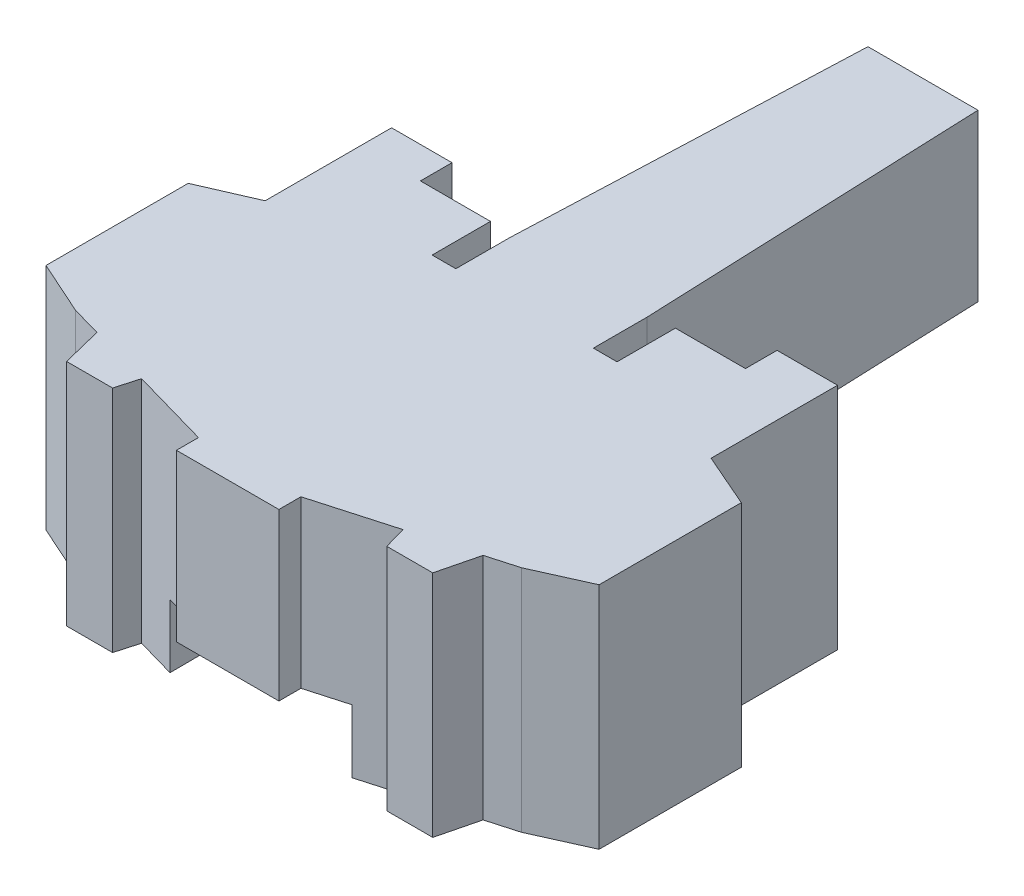
SolidWorks part; units mm, degrees
ref_plane "Front Plane" through (0, 0, 0) normal (0, 0, 1) x (1, 0, 0)
ref_plane "Top Plane" through (0, 0, 0) normal (0, 1, 0) x (1, 0, 0)
ref_plane "Right Plane" through (0, 0, 0) normal (1, 0, 0) x (0, 0, -1)
sketch "Sketch1" plane through (0, 0, 0) normal (0, 1, 0) x (1, 0, 0)
  line L0 (189.3756, 496.5449) -> (821.9605, 485.5031) construction
  line L1 (66.1046, 65.3579) -> (66.1046, 21.3579) construction
  line L2 (69.5865, 65.3579) -> (62.6228, 65.3579)
  line L3 (69.5865, 65.3579) -> (70.4558, 43.5381)
  line L4 (70.4558, 43.5381) -> (70.4558, 40.1478)
  line L5 (70.4558, 40.1478) -> (71.9558, 40.1478)
  line L6 (71.9558, 40.1478) -> (71.9558, 43.8392)
  line L7 (71.9558, 43.8392) -> (76.3893, 43.8392)
  line L8 (76.3893, 43.8392) -> (76.3893, 45.8392)
  line L9 (76.3893, 45.8392) -> (80.2143, 45.8392)
  line L10 (80.2143, 45.8392) -> (80.2143, 37.8392)
  line L11 (80.2143, 37.8392) -> (83.6046, 36.3613)
  line L12 (83.6046, 36.3613) -> (83.6046, 27.3613)
  line L13 (83.6046, 27.3613) -> (80.2143, 25.8392)
  line L14 (80.2143, 25.8392) -> (78.3232, 25.3017)
  line L15 (69.3478, 22.751) -> (69.3478, 21.3579)
  line L16 (69.3478, 21.3579) -> (62.8614, 21.3579)
  line L17 (62.8614, 22.751) -> (62.8614, 21.3579)
  line L18 (51.9949, 25.8392) -> (53.8861, 25.3017)
  line L19 (48.6046, 27.3613) -> (51.9949, 25.8392)
  line L20 (48.6046, 36.3613) -> (48.6046, 27.3613)
  line L21 (51.9949, 37.8392) -> (48.6046, 36.3613)
  line L22 (51.9949, 45.8392) -> (51.9949, 37.8392)
  line L23 (55.8199, 45.8392) -> (51.9949, 45.8392)
  line L24 (55.8199, 43.8392) -> (55.8199, 45.8392)
  line L25 (60.2534, 43.8392) -> (55.8199, 43.8392)
  line L26 (60.2534, 40.1478) -> (60.2534, 43.8392)
  line L27 (61.7534, 40.1478) -> (60.2534, 40.1478)
  line L28 (61.7534, 43.5381) -> (61.7534, 40.1478)
  line L29 (62.6228, 65.3579) -> (61.7534, 43.5381)
  line L30 (78.3232, 25.3017) -> (77.6888, 22.751)
  line L31 (77.6888, 22.751) -> (74.7811, 22.751)
  line L32 (74.7811, 22.751) -> (74.375, 24.1797)
  line L33 (74.375, 24.1797) -> (69.3478, 22.751)
  line L34 (53.8861, 25.3017) -> (54.5204, 22.751)
  line L35 (54.5204, 22.751) -> (57.4282, 22.751)
  line L36 (57.4282, 22.751) -> (57.8342, 24.1797)
  line L37 (57.8342, 24.1797) -> (62.8614, 22.751)
  dimension "D1" = 17.5
  dimension "D2" = 12
  dimension "D3" = 3.0881
  dimension "D4" = 1.4778
  dimension "D5" = 8
  dimension "D6" = 2
  dimension "D7" = 1.5
  dimension "D8" = 14.2568
  dimension "D9" = 3.825
  dimension "D10" = 4.4335
  dimension "D11" = 3.4819
  dimension "D12" = 44
  dimension "D13" = 9
  dimension "D14" = 48.6046
  dimension "D15" = 51.9949
  dimension "D16" = 53.8861
  dimension "D17" = 54.5204
  dimension "D18" = 57.4282
  dimension "D19" = 21.3579
  dimension "D20" = 22.751
  dimension "D23" = 40.1478
  dimension "D24" = 43.5381
extrude "Boss-Extrude1" add sketch "Sketch1" along normal blind 14.5
sketch "Sketch2" plane through (0, 0, 0) normal (0, -1, 0) x (-1, 0, 0)
  line L0 (-66.1046, 21.3579) -> (-66.1046, 65.3579) construction
  line L1 (-62.8614, 21.3579) -> (-69.3478, 21.3579) construction
  line L2 (-69.5865, 65.3579) -> (-62.6228, 65.3579) construction
  line L3 (-60.2534, 40.1478) -> (-60.3478, 23.4654)
  line L4 (-57.8342, 24.1797) -> (-62.8614, 22.751) construction
  line L5 (-60.3478, 23.4654) -> (-62.8614, 22.751)
  line L6 (-62.8614, 22.751) -> (-62.8614, 21.3579)
  line L7 (-62.8614, 21.3579) -> (-69.3478, 21.3579)
  line L8 (-69.3478, 21.3579) -> (-69.3478, 22.751)
  line L9 (-69.3478, 22.751) -> (-71.8614, 23.4654)
  line L10 (-69.3478, 22.751) -> (-74.375, 24.1797) construction
  line L11 (-71.8614, 23.4654) -> (-71.9558, 40.1478)
  line L12 (-71.9558, 40.1478) -> (-70.4558, 40.1478)
  line L13 (-70.4558, 40.1478) -> (-70.4558, 43.5381)
  line L14 (-70.4558, 43.5381) -> (-69.5865, 65.3579)
  line L15 (-69.5865, 65.3579) -> (-62.6228, 65.3579)
  line L16 (-62.6228, 65.3579) -> (-61.7534, 43.5381)
  line L17 (-61.7534, 43.5381) -> (-61.7534, 40.1478)
  line L18 (-61.7534, 40.1478) -> (-60.2534, 40.1478)
  line L19 (-48.6046, 36.3613) -> (-48.6046, 27.3613) construction
  circle A0 centre (-66.1046, 40.8079) radius 2.5
  dimension "D1" = 5
  dimension "D2" = 13.6103
  dimension "D3" = 18.0569
extrude "Cut-Extrude1" cut sketch "Sketch2" against normal blind 4
